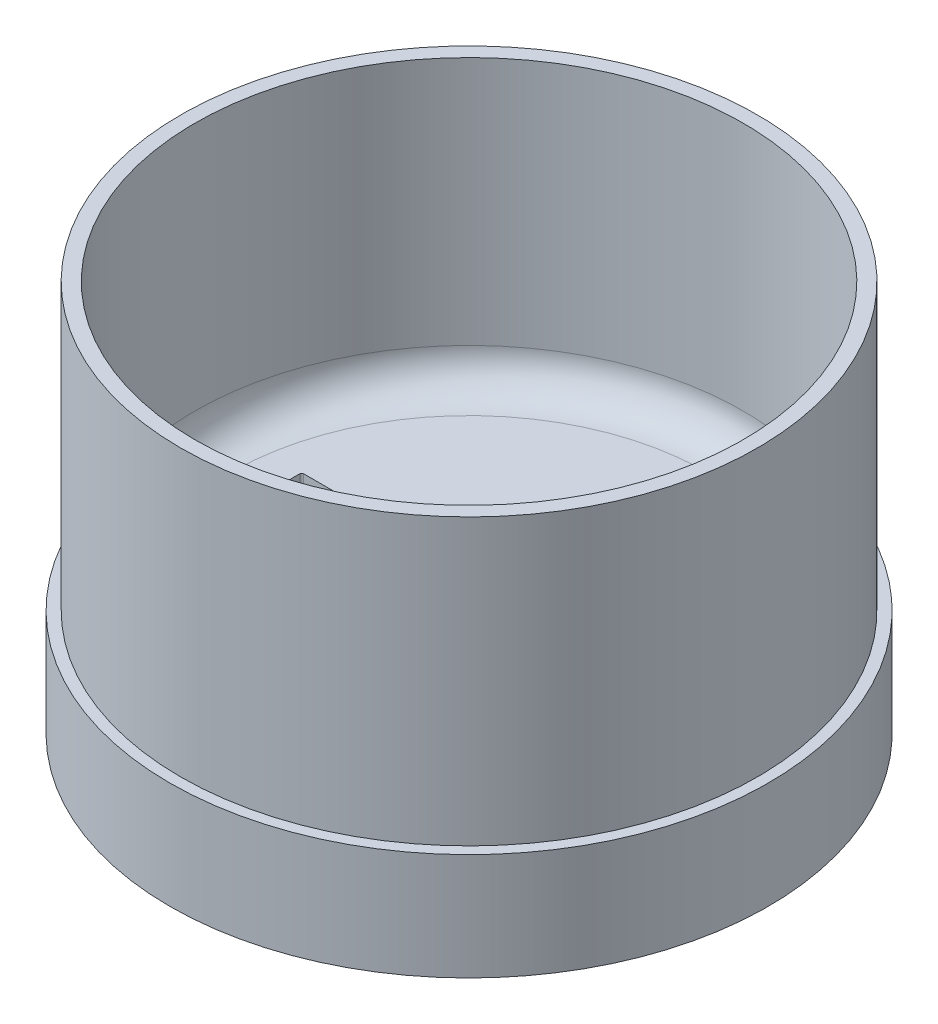
SolidWorks part; units mm, degrees
material "PET"
ref_plane "Front Plane" through (0, 0, 0) normal (0, 0, 1) x (1, 0, 0)
ref_plane "Top Plane" through (0, 0, 0) normal (0, 1, 0) x (1, 0, 0)
ref_plane "Right Plane" through (0, 0, 0) normal (1, 0, 0) x (0, 0, -1)
sketch "Sketch1" plane through (0, 0, 0) normal (0, 1, 0) x (1, 0, 0)
  circle A0 centre (0, 0) radius 84
  circle A1 centre (0, 0) radius 79
extrude "Boss-Extrude1" add sketch "Sketch1" along normal blind 25
sketch "Sketch2" plane through (0, 25, 0) normal (0, 1, 0) x (1, 0, 0)
  circle A0 centre (0, 0) radius 84
extrude "Boss-Extrude2" add sketch "Sketch2" along normal blind 5
sketch "Sketch3" plane through (0, 30, 0) normal (0, 1, 0) x (1, 0, 0)
  circle A0 centre (0, 0) radius 81
  circle A1 centre (0, 0) radius 77
extrude "Boss-Extrude3" add sketch "Sketch3" along normal blind 80
fillet "Fillet1" radius 10 2 edges at (0, 25, 79) (0, 30, 77)
sketch "Sketch4" plane through (0, 25, 0) normal (0, -1, 0) x (1, 0, 0)
  line L1 (7, -3.5) -> (7, 3.5)
  line L2 (7, 3.5) -> (-7, 3.5)
  line L3 (-7, 3.5) -> (-7, -3.5)
  line L4 (-7, -3.5) -> (7, -3.5)
  point P4 (0, 0)
  point P8 (7, 0)
extrude "Cut-Extrude1" cut sketch "Sketch4" against normal up to next
sketch "Sketch5" plane through (0, 30, 0) normal (0, 1, 0) x (1, 0, 0)
  line L0 (0, 0) -> (-43, 0) construction
  line L1 (-43, -10) -> (-43, 10)
  line L2 (-43, 10) -> (-57, 10)
  line L3 (-57, 10) -> (-57, -10)
  line L4 (-57, -10) -> (-43, -10)
  point P7 (-43, 0)
extrude "Cut-Extrude2" cut sketch "Sketch5" against normal up to next
fillet "Fillet2" radius 1 8 edges at (-7, 25, 0) (0, 25, 3.5) (7, 25, 0) (0, 25, -3.5) (-7, 30, 0) (0, 30, 3.5) (7, 30, 0) (0, 30, -3.5)
fillet "Fillet3" radius 0.5 4 edges at (-43, 27.5, 10) (-57, 27.5, 10) (-43, 27.5, -10) (-57, 27.5, -10)
